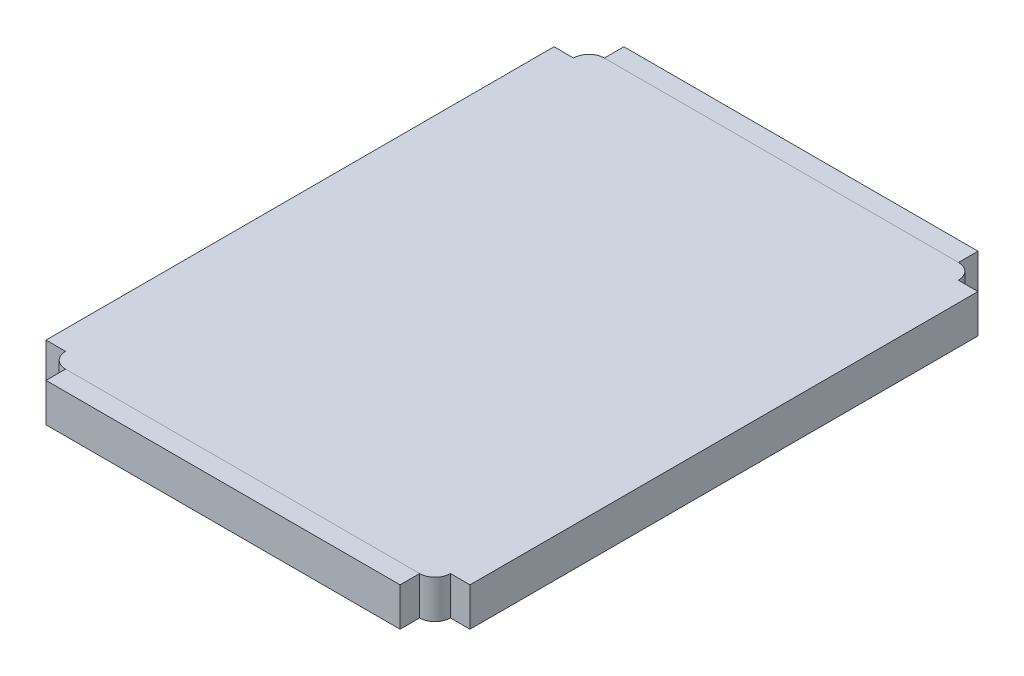
SolidWorks part; units mm, degrees
ref_plane "Front Plane" through (0, 0, 0) normal (0, 0, 1) x (1, 0, 0)
ref_plane "Top Plane" through (0, 0, 0) normal (0, 1, 0) x (1, 0, 0)
ref_plane "Right Plane" through (0, 0, 0) normal (1, 0, 0) x (0, 0, -1)
sketch "Sketch1" plane through (0, 836.5359, 0) normal (0, -1, 0) x (1, 0, 0)
  line L0 (675.181, 1276.1699) -> (675.181, 1329.1699) construction
  line L1 (655.681, 1276.1699) -> (694.6809, 1276.1699) construction
  line L2 (694.681, 1329.1699) -> (655.681, 1329.1699) construction
  line L4 (655.6809, 1276.1699) -> (694.681, 1276.1699)
  line L5 (651.6809, 1280.1699) -> (651.6809, 1325.1699)
  line L6 (655.6809, 1329.1699) -> (694.681, 1329.1699)
  line L7 (698.681, 1280.1699) -> (698.681, 1325.1699)
  line L8 (651.6809, 1276.1699) -> (698.681, 1329.1699) construction
  line L9 (651.6809, 1329.1699) -> (698.681, 1276.1699) construction
  arc A0 (651.6809, 1325.1699) -> (655.6809, 1329.1699) centre (655.6809, 1325.1699) cw
  arc A1 (655.6809, 1276.1699) -> (651.6809, 1280.1699) centre (655.6809, 1280.1699) cw
  arc A2 (694.681, 1276.1699) -> (698.681, 1280.1699) centre (694.681, 1280.1699) ccw
  arc A3 (694.681, 1329.1699) -> (698.681, 1325.1699) centre (694.681, 1325.1699) cw
  point P6 (675.181, 1302.6699)
  dimension "D3" = 4
  dimension "D1" = 53
  dimension "D2" = 47
extrude "Boss-Extrude1" add sketch "Sketch1" along normal blind 3.81
sketch "Sketch2" plane through (0, 836.5359, 0) normal (0, 1, 0) x (1, 0, 0)
  line L0 (651.6809, -1280.1699) -> (651.6809, -1325.1699) construction
  line L1 (694.6809, -1276.1699) -> (655.681, -1276.1699) construction
  line L2 (698.681, -1280.1699) -> (698.681, -1325.1699) construction
  circle A0 centre (655.6809, -1280.1699) radius 1.4
  circle A1 centre (694.6809, -1280.1699) radius 1.4
  circle A2 centre (694.681, -1325.1699) radius 1.4
  circle A3 centre (655.681, -1325.1699) radius 1.4
  point P8 (0, 0)
  point P11 (0, 0)
  dimension "D1" = 2.8
  dimension "D2" = 39
  dimension "D3" = 45
  dimension "D4" = 4
  dimension "D5" = 4
  dimension "D6" = 45
  dimension "D7" = 39
  dimension "D8" = 4
  dimension "D9" = 4
sketch "Sketch4" plane through (0, 868.1359, 0) normal (0, -1, 0) x (1, 0, 0)
  line L1 (652.181, 1336.5723) -> (698.181, 1336.5723)
  line L2 (650.181, 1334.5723) -> (650.181, 1268.5723)
  line L3 (652.181, 1266.5723) -> (698.181, 1266.5723)
  line L4 (700.181, 1334.5723) -> (700.181, 1268.5723)
  line L5 (650.181, 1336.5723) -> (700.181, 1266.5723) construction
  line L6 (650.181, 1266.5723) -> (700.181, 1336.5723) construction
  arc A0 (650.181, 1268.5723) -> (652.181, 1266.5723) centre (652.181, 1268.5723) ccw
  arc A1 (698.181, 1266.5723) -> (700.181, 1268.5723) centre (698.181, 1268.5723) ccw
  arc A2 (698.181, 1336.5723) -> (700.181, 1334.5723) centre (698.181, 1334.5723) cw
  arc A3 (652.181, 1336.5723) -> (650.181, 1334.5723) centre (652.181, 1334.5723) ccw
  point P4 (675.181, 1301.5723)
  dimension "D1" = 2
extrude "Boss-Extrude4" add sketch "Sketch4" along normal blind 5 separate body
ref_plane "Plane1" through (0, 0, 1302.6699) normal (0, 0, 1) x (1, 0, 0)
extrude "Boss-Extrude5" add sketch "Sketch2" along normal blind 5
sketch "Sketch6" plane through (0, 832.7259, 0) normal (0, -1, 0) x (1, 0, 0)
  line L0 (675.181, 1329.1699) -> (675.181, 1276.1699) construction
  line L1 (694.681, 1329.1699) -> (655.6809, 1329.1699) construction
  line L2 (655.6809, 1276.1699) -> (694.681, 1276.1699) construction
sketch "Sketch8" plane through (0, 868.1359, 0) normal (0, 1, 0) x (1, 0, 0)
  line L0 (650.181, -1268.5723) -> (650.181, -1334.5723)
  line L1 (650.181, -1268.5723) -> (647.641, -1268.5723)
  line L2 (650.181, -1334.5723) -> (647.641, -1334.5723)
  line L3 (647.641, -1268.5723) -> (647.641, -1334.5723)
  line L4 (652.181, -1266.5723) -> (698.181, -1266.5723)
  line L5 (652.181, -1266.5723) -> (652.181, -1264.0323)
  line L6 (698.181, -1266.5723) -> (698.181, -1264.0323)
  line L7 (652.181, -1264.0323) -> (698.181, -1264.0323)
  line L8 (650.181, -1301.5723) -> (700.181, -1301.5723) construction
  line L9 (700.181, -1268.5723) -> (700.181, -1334.5723) construction
  line L10 (652.181, -1339.1123) -> (698.181, -1339.1123)
  line L11 (698.181, -1336.5723) -> (698.181, -1339.1123)
  line L12 (652.181, -1336.5723) -> (652.181, -1339.1123)
  line L13 (652.181, -1336.5723) -> (698.181, -1336.5723)
  line L14 (675.181, -1329.1699) -> (675.181, -1276.1699) construction
  line L15 (702.7209, -1268.5723) -> (702.7209, -1334.5723)
  line L16 (700.1809, -1334.5723) -> (702.7209, -1334.5723)
  line L17 (700.1809, -1268.5723) -> (702.7209, -1268.5723)
  line L18 (700.1809, -1268.5723) -> (700.1809, -1334.5723)
  dimension "D1" = 2.54
extrude "Boss-Extrude7" add sketch "Sketch8" against normal up to surface (5 mm away) separate body up to face at (675.181, 863.1359, 1301.5723)
sketch "Sketch10" plane through (0, 832.7259, 0) normal (0, -1, 0) x (1, 0, 0)
  line L0 (651.6809, 1325.1699) -> (651.6809, 1280.1699)
  line L1 (651.6809, 1325.1699) -> (649.1409, 1325.1699)
  line L2 (651.6809, 1280.1699) -> (649.1409, 1280.1699)
  line L3 (649.1409, 1325.1699) -> (649.1409, 1280.1699)
  line L4 (655.6809, 1329.1699) -> (694.681, 1329.1699)
  line L5 (655.6809, 1329.1699) -> (655.6809, 1331.7099)
  line L6 (694.681, 1329.1699) -> (694.681, 1331.7099)
  line L7 (655.6809, 1331.7099) -> (694.681, 1331.7099)
  line L8 (698.681, 1325.1699) -> (698.681, 1280.1699)
  line L9 (698.681, 1325.1699) -> (701.221, 1325.1699)
  line L10 (698.681, 1280.1699) -> (701.221, 1280.1699)
  line L11 (701.221, 1325.1699) -> (701.221, 1280.1699)
  line L12 (694.681, 1276.1699) -> (655.6809, 1276.1699)
  line L13 (694.681, 1276.1699) -> (694.681, 1273.6299)
  line L14 (655.6809, 1276.1699) -> (655.6809, 1273.6299)
  line L15 (694.681, 1273.6299) -> (655.6809, 1273.6299)
  line L16 (655.6809, 1276.1699) -> (694.681, 1276.1699) construction
  arc A0 (694.681, 1276.1699) -> (698.681, 1280.1699) centre (694.681, 1280.1699) ccw construction
  arc A1 (651.6809, 1280.1699) -> (655.6809, 1276.1699) centre (655.6809, 1280.1699) ccw construction
  dimension "D1" = 2.54
extrude "Boss-Extrude8" add sketch "Sketch10" against normal up to surface (3.81 mm away) separate body up to face at (654.281, 836.5359, 1325.1699)
loft "Loft6" add section face at (648.911, 863.1359, 1301.5723) section face at (650.4109, 836.5359, 1302.6699) connector at (647.641, 863.1359, 1334.5723) connector at (649.1409, 836.5359, 1325.1699)
loft "Loft8" add section face at (701.4509, 863.1359, 1301.5723) section face at (699.951, 836.5359, 1302.6699) start constraint default connector at (700.1809, 863.1359, 1334.5723) connector at (698.681, 836.5359, 1325.1699)
sketch "Sketch11" plane through (694.1061, 39.1407, 0) normal (-0.9984, -0.0563, 0) x (0, 0, 1)
sketch "Sketch12" plane through (0, 0, 1339.1123) normal (0, 0, 1) x (1, 0, 0)
  line L0 (647.641, 863.1359) -> (702.7209, 863.1359)
  line L1 (647.641, 863.1359) -> (647.641, 830.2485)
  line L2 (702.7209, 863.1359) -> (702.7209, 830.2485)
  line L3 (647.641, 830.2485) -> (702.7209, 830.2485)
extrude "Cut-Extrude1" cut sketch "Sketch12" against normal through all
